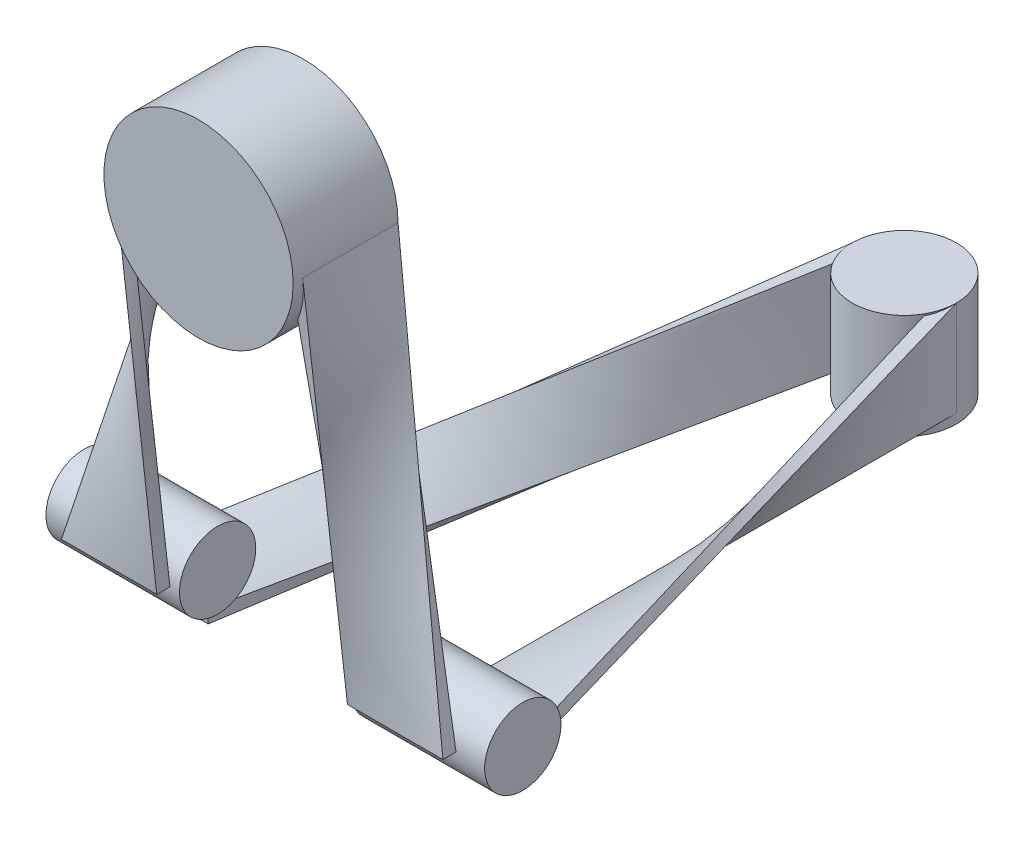
SolidWorks part; units mm, degrees
ref_plane "Front" through (0, 0, 0) normal (0, 0, 1) x (1, 0, 0)
ref_plane "Top" through (0, 0, 0) normal (0, 1, 0) x (1, 0, 0)
ref_plane "Right" through (0, 0, 0) normal (1, 0, 0) x (0, 0, -1)
sketch "Эскиз1" plane through (0, 0, 0) normal (0, 0, 1) x (1, 0, 0)
  circle A0 centre (0, 0) radius 9.9198
  dimension "D1" = 19.8396
extrude "Бобышка-Вытянуть1" add sketch "Эскиз1" along normal blind 11
ref_plane "Плоскость1" through (0, -41, 0) normal (0, 1, 0) x (1, 0, 0)
sketch "Эскиз3" plane through (0, -41, 0) normal (0, 1, 0) x (1, 0, 0)
  line L0 (0, 0) -> (0, 63)
  line L1 (0, -50) -> (0, 50) construction
  circle A0 centre (0, 63) radius 5.4635
  dimension "D1" = 10.9269
  dimension "D2" = 63
extrude "Бобышка-Вытянуть2" add sketch "Эскиз3" against normal blind 11 separate body contours A0 region at (3.754, -41, -59.246)
sketch "Эскиз4" plane through (0, 0, 0) normal (1, 0, 0) x (0, 0, -1)
  line L1 (0, 0) -> (0, -41)
  circle A0 centre (0, -41) radius 4
  dimension "D1" = 41
extrude "Бобышка-Вытянуть3" add sketch "Эскиз4" along normal blind 14 from offset 9 separate body contours A0
extrude "Бобышка-Вытянуть4" add sketch "Эскиз4<3>" against normal blind 14 from offset 9 separate body contours A0 region at (0, -43.7484, 2.7484) offset against normal yes
sketch "Эскиз4<3>" plane through (0, 0, 0) normal (1, 0, 0) x (0, 0, -1) same geometry as "Эскиз4"
sketch "Эскиз5" plane through (0, 0, 0) normal (0, 1, 0) x (1, 0, 0)
  line L0 (0, 0) -> (9.9198, 0) construction
  line L1 (-50, 0) -> (50, 0) construction
  line L2 (9.9198, -11) -> (9.9198, 0) construction
  line L5 (9.9198, -10) -> (8.5398, -10)
  line L6 (8.5398, -10) -> (8.5398, 0)
  line L7 (8.5398, 0) -> (9.9198, 0)
  line L9 (9.9198, -10) -> (9.9198, 0)
  point P9 (9.9198, -5)
ref_plane "Плоскость2" through (0, -41, 0) normal (0, 1, 0) x (1, 0, 0)
sketch "Эскиз6" plane through (0, -41, 0) normal (0, 1, 0) x (1, 0, 0)
  line L0 (0, -7) -> (15, -7) construction
  line L1 (0, -50) -> (0, 50) construction
  line L2 (15, -7) -> (15, -4) construction
  line L3 (9, -4) -> (23, -4) construction
  line L4 (0, -7) -> (-15, -7) construction
  line L5 (-15, -7) -> (-15, 0) construction
  line L7 (10, -4) -> (10, -5.38)
  line L8 (10, -5.38) -> (20, -5.38)
  line L9 (20, -5.38) -> (20, -4)
  line L11 (10, -4) -> (20, -4)
  dimension "D1" = 10
  dimension "D2" = 1.38
  dimension "D3" = 7
loft "По сечениям1" add section "Эскиз5" section "Эскиз6" connector at (9.9198, 0, 10) connector at (10, -41, 5.38)
ref_plane "Плоскость3" through (0, 0, 0) normal (0, 0, 1) x (1, 0, 0)
sketch "Эскиз7" plane through (0, 0, 0) normal (0, 0, 1) x (1, 0, 0)
  line L0 (0, 0) -> (0, -41) construction
  line L1 (50, -41) -> (-50, -41) construction
  line L2 (0, -50) -> (0, 50) construction
  line L3 (0, -41) -> (15, -41) construction
  line L4 (15, -41) -> (15, -45) construction
  line L6 (20, -45) -> (20, -46.38)
  line L7 (20, -46.38) -> (10, -46.38)
  line L8 (10, -46.38) -> (10, -45)
  line L10 (10, -45) -> (20, -45)
  dimension "D1" = 4
  dimension "D2" = 10
  dimension "D3" = 1.38
ref_plane "Плоскость4" through (0, 0, -63) normal (0, 0, 1) x (1, 0, 0)
sketch "Эскиз9" plane through (0, 0, -63) normal (0, 0, 1) x (1, 0, 0)
  line L0 (0, 0) -> (0, -41)
  line L1 (0, -51) -> (12.5746, -51) construction
  line L4 (0, 0) -> (0, -41) construction
  line L5 (50, -41) -> (-50, -41) construction
  line L6 (0, -41) -> (0, -51)
  line L8 (5.4635, -52) -> (5.4635, -41) construction
  line L9 (5.4635, -51) -> (5.4635, -41)
  line L10 (5.4635, -41) -> (4.0835, -41)
  line L11 (4.0835, -41) -> (4.0835, -51)
  line L12 (4.0835, -51) -> (5.4635, -51)
  dimension "D1" = 10
  dimension "D2" = 1.38
loft "По сечениям3" add section "Эскиз7" section "Эскиз9" connector at (20, -46.38, 0) connector at (5.4635, -41, -63)
mirror "Зеркальное отражение7" about plane through (0, 0, 0) normal (1, 0, 0) of bodies 107 105
